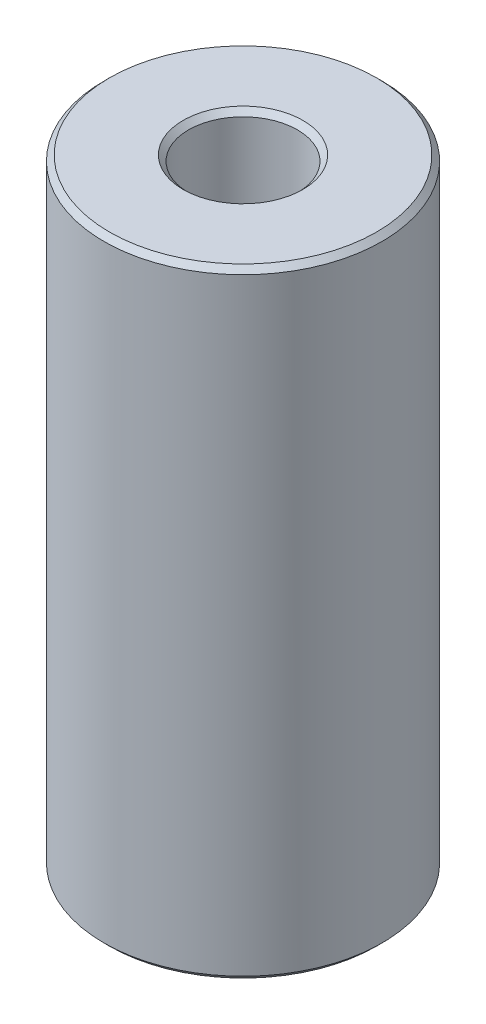
SolidWorks part; units mm, degrees
ref_plane "Front Plane" through (0, 0, 0) normal (0, 0, 1) x (1, 0, 0)
ref_plane "Top Plane" through (0, 0, 0) normal (0, 1, 0) x (1, 0, 0)
ref_plane "Right Plane" through (0, 0, 0) normal (1, 0, 0) x (0, 0, -1)
sketch "Sketch1" plane through (0, 0, 0) normal (0, 1, 0) x (1, 0, 0)
  circle A0 centre (0, 0) radius 12.5
  dimension "SLEEVE_OD" = 25
extrude "Boss-Extrude1" add sketch "Sketch1" along normal blind 55.6069
sketch "Sketch2" plane through (0, 0, 0) normal (0, 1, 0) x (1, 0, 0)
  circle A0 centre (0, 0) radius 4.8946
  dimension "BORE_D" = 9.7892
extrude "Cut-Extrude1" cut sketch "Sketch2" along normal through all
chamfer "Chamfer1" distance 0.4905 angle 45 4 edges at (0, 55.6069, 4.8946) (0, 0, 4.8946) (0, 0, 12.5) (0, 55.6069, 12.5)
